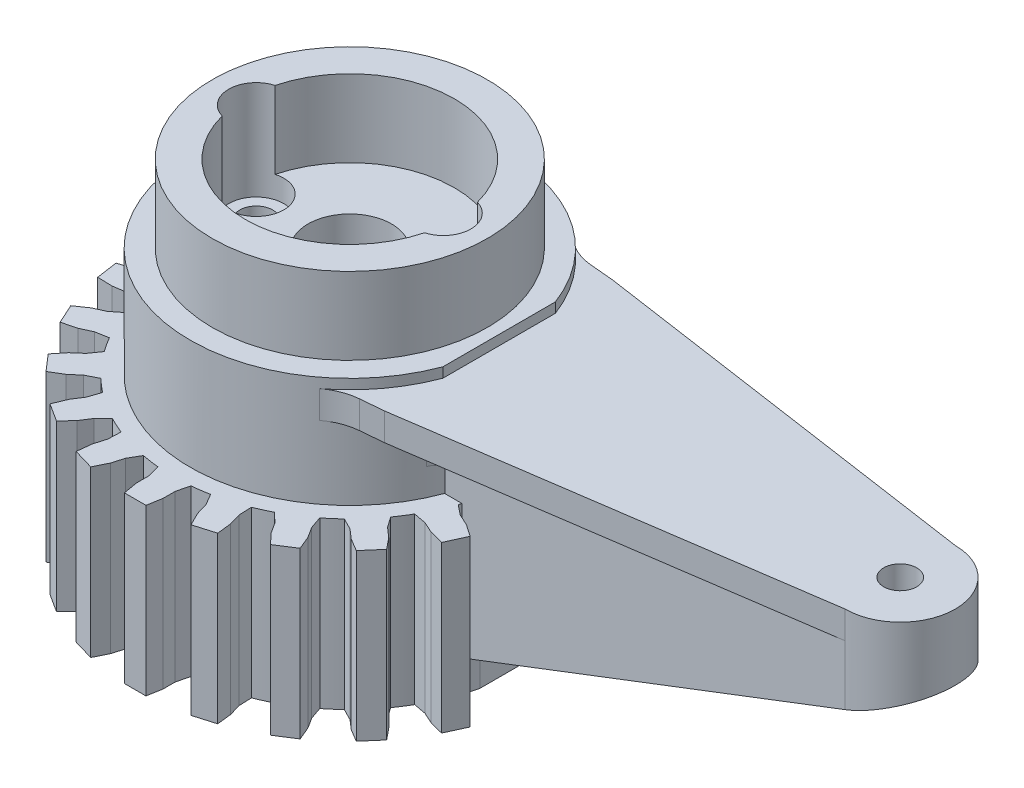
SolidWorks part; units mm, degrees
other "Markup1"
sketch "Sketch11" plane through (-17.3474, -40, -17.5082) normal (-0.1763, -0.9804, -0.0883) x (-0.1909, 0.1221, -0.974)
ref_plane "Front Plane" through (0, 0, 0) normal (0, 0, 1) x (1, 0, 0)
ref_plane "Top Plane" through (0, 0, 0) normal (0, 1, 0) x (1, 0, 0)
ref_plane "Right Plane" through (0, 0, 0) normal (1, 0, 0) x (0, 0, -1)
sketch "Sketch1" plane through (0, 0, 0) normal (0, 1, 0) x (1, 0, 0)
  circle A0 centre (0, 0) radius 14.5
extrude "Boss-Extrude1" add sketch "Sketch1" along normal blind 2 contours A0
sketch "Sketch2" plane through (0, 2, 0) normal (0, 1, 0) x (1, 0, 0)
  line L0 (0, 0) -> (-8.5, 0) construction
  line L1 (0, 0) -> (0, -2.0986) construction
  circle A0 centre (0, 0) radius 3.8
  circle A1 centre (-8.5, 0) radius 1.5
  circle A2 centre (8.5, 0) radius 1.5
  dimension "D1" = 8.5
extrude "Cut-Extrude1" cut sketch "Sketch2" against normal blind 2.5
sketch "Sketch3" plane through (0, 0, 0) normal (0, -1, 0) x (1, 0, 0)
  circle A0 centre (0, 0) radius 14.5
  circle A1 centre (0, 0) radius 12.5
  circle M3 centre (8.5, 0) radius 1.5
  circle M4 centre (-8.5, 0) radius 1.5
  circle M5 centre (0, 0) radius 3.8
  dimension "D1" = 2
extrude "Boss-Extrude2" add sketch "Sketch3" along normal blind 7 contours A1 M3 M5 M4 | A0 region at (-12.1464, 0, 0)
sketch "Sketch4" plane through (0, 2, 0) normal (0, 1, 0) x (1, 0, 0)
  circle A0 centre (0, 0) radius 3.8
  circle A1 centre (8.5, 0) radius 1.5
  circle A2 centre (-8.5, 0) radius 1.5
  circle A3 centre (0, 0) radius 14.5
extrude "Boss-Extrude3" add sketch "Sketch4" along normal blind 1 contours A3 | A2 | A1 | A0
sketch "Sketch5" plane through (0, 3, 0) normal (0, 1, 0) x (1, 0, 0)
  line L0 (0, 0) -> (0, 9.3425) construction
  circle A0 centre (8.5, 0) radius 2.6
  circle A1 centre (-8.5, 0) radius 2.5
extrude "Cut-Extrude2" cut sketch "Sketch5" against normal blind 2
sketch "Sketch6" plane through (0, 3, 0) normal (0, 1, 0) x (1, 0, 0)
  line L0 (0, 0) -> (30, 0) construction
  line L1 (30, 0) -> (45, 0) construction
  line L2 (45, 0) -> (60, 0) construction
  line L3 (60, 5) -> (13.6107, 5)
  line L4 (60, -5) -> (13.6107, -5)
  line L5 (60, 0) -> (73, 0) construction
  line L6 (60, 5) -> (70, 5)
  line L7 (60, -5) -> (70, -5)
  line L8 (70, 5) -> (73, 5)
  line L9 (70, -5) -> (73, -5)
  circle A4 centre (0, 0) radius 14.5 construction
  circle A6 centre (73, 0) radius 1.5
  arc A8 (73, -5) -> (73, 5) centre (73, 0) ccw
  circle M3 centre (0, 0) radius 14.5
  dimension "D1" = 15
  dimension "D2" = 15
  dimension "D3" = 30
  dimension "D4" = 13
extrude "Boss-Extrude4" add sketch "Sketch6" against normal blind 3.5 contours L4 L3 M3 region at (45.2639, 3, 0)
sketch "Sketch9" plane through (0, -7, 0) normal (0, -1, 0) x (-1, 0, 0)
  line L0 (0, 15.9926) -> (0, 19.4946) construction
  line L1 (0.9773, 19.4946) -> (-0.9773, 19.4946)
  line L2 (-0.9773, 19.4946) -> (-1.2082, 18.1848)
  line L45 (-0.9773, 19.4946) -> (-0.9773, 18.0837) construction
  line L46 (-1.2082, 18.1848) -> (-1.2082, 17.0658)
  line L47 (-1.2082, 17.0658) -> (-1.4932, 15.9228)
  line L48 (-1.2082, 17.0658) -> (-1.2082, 16.2048) construction
  line L49 (1.2082, 17.0658) -> (1.4932, 15.9228)
  line L50 (1.2082, 18.1848) -> (1.2082, 17.0658)
  line L51 (0.9773, 19.4946) -> (1.2082, 18.1848)
  line L52 (5.9673, 16.0341) -> (5.9187, 14.8571)
  line L53 (6.2825, 17.1078) -> (5.9673, 16.0341)
  line L54 (6.4299, 18.4296) -> (6.2825, 17.1078)
  line L55 (6.4299, 18.4296) -> (4.5546, 18.9802)
  line L56 (4.5546, 18.9802) -> (3.964, 17.7886)
  line L57 (3.964, 17.7886) -> (3.6487, 16.7149)
  line L58 (3.6487, 16.7149) -> (3.0533, 15.6985)
  line L59 (10.2429, 13.7034) -> (9.8646, 12.5878)
  line L60 (10.8478, 14.6448) -> (10.2429, 13.7034)
  line L61 (11.3617, 15.8715) -> (10.8478, 14.6448)
  line L62 (11.3617, 15.8715) -> (9.7174, 16.9282)
  line L63 (9.7174, 16.9282) -> (8.815, 15.9512)
  line L64 (8.815, 15.9512) -> (8.21, 15.0098)
  line L65 (8.21, 15.0098) -> (7.3523, 14.2024)
  line L66 (13.6887, 10.2626) -> (13.0115, 9.2987)
  line L67 (14.5343, 10.9954) -> (13.6887, 10.2626)
  line L68 (15.373, 12.0277) -> (14.5343, 10.9954)
  line L69 (15.373, 12.0277) -> (14.093, 13.5048)
  line L70 (14.093, 13.5048) -> (12.9519, 12.8216)
  line L71 (12.9519, 12.8216) -> (12.1062, 12.0888)
  line L72 (12.1062, 12.0888) -> (11.0558, 11.5557)
  line L73 (16.0255, 5.9904) -> (15.1042, 5.2563)
  line L74 (17.0434, 6.4552) -> (16.0255, 5.9904)
  line L75 (18.1389, 7.2094) -> (17.0434, 6.4552)
  line L76 (18.1389, 7.2094) -> (17.3269, 8.9873)
  line L77 (17.3269, 8.9873) -> (16.0395, 8.6533)
  line L78 (16.0395, 8.6533) -> (15.0217, 8.1884)
  line L79 (15.0217, 8.1884) -> (13.8636, 7.9728)
  line L80 (17.064, 1.2328) -> (15.9732, 0.7881)
  line L81 (18.1716, 1.3921) -> (17.064, 1.2328)
  line L82 (19.4352, 1.8071) -> (18.1716, 1.3921)
  line L83 (19.4352, 1.8071) -> (19.1571, 3.7417)
  line L84 (19.1571, 3.7417) -> (17.8277, 3.7839)
  line L85 (17.8277, 3.7839) -> (16.7201, 3.6246)
  line L86 (16.7201, 3.6246) -> (15.5482, 3.744)
  line L87 (16.7201, -3.6246) -> (15.5482, -3.744)
  line L88 (17.8277, -3.7839) -> (16.7201, -3.6246)
  line L89 (19.1571, -3.7417) -> (17.8277, -3.7839)
  line L90 (19.1571, -3.7417) -> (19.4352, -1.8071)
  line L91 (19.4352, -1.8071) -> (18.1716, -1.3921)
  line L92 (18.1716, -1.3921) -> (17.064, -1.2328)
  line L93 (17.064, -1.2328) -> (15.9732, -0.7881)
  line L94 (15.0217, -8.1884) -> (13.8636, -7.9728)
  line L95 (16.0395, -8.6533) -> (15.0217, -8.1884)
  line L96 (17.3269, -8.9873) -> (16.0395, -8.6533)
  line L97 (17.3269, -8.9873) -> (18.1389, -7.2094)
  line L98 (18.1389, -7.2094) -> (17.0434, -6.4552)
  line L99 (17.0434, -6.4552) -> (16.0255, -5.9904)
  line L100 (16.0255, -5.9904) -> (15.1042, -5.2563)
  line L101 (12.1062, -12.0888) -> (11.0558, -11.5557)
  line L102 (12.9519, -12.8216) -> (12.1062, -12.0888)
  line L103 (14.093, -13.5048) -> (12.9519, -12.8216)
  line L104 (14.093, -13.5048) -> (15.373, -12.0277)
  line L105 (15.373, -12.0277) -> (14.5343, -10.9954)
  line L106 (14.5343, -10.9954) -> (13.6887, -10.2626)
  line L107 (13.6887, -10.2626) -> (13.0115, -9.2987)
  line L108 (8.21, -15.0098) -> (7.3523, -14.2024)
  line L109 (8.815, -15.9512) -> (8.21, -15.0098)
  line L110 (9.7174, -16.9282) -> (8.815, -15.9512)
  line L111 (9.7174, -16.9282) -> (11.3617, -15.8715)
  line L112 (11.3617, -15.8715) -> (10.8478, -14.6448)
  line L113 (10.8478, -14.6448) -> (10.2429, -13.7034)
  line L114 (10.2429, -13.7034) -> (9.8646, -12.5878)
  line L115 (3.6487, -16.7149) -> (3.0533, -15.6985)
  line L116 (3.964, -17.7886) -> (3.6487, -16.7149)
  line L117 (4.5546, -18.9802) -> (3.964, -17.7886)
  line L118 (4.5546, -18.9802) -> (6.4299, -18.4296)
  line L119 (6.4299, -18.4296) -> (6.2825, -17.1078)
  line L120 (6.2825, -17.1078) -> (5.9673, -16.0341)
  line L121 (5.9673, -16.0341) -> (5.9187, -14.8571)
  line L122 (-1.2082, -17.0658) -> (-1.4932, -15.9228)
  line L123 (-1.2082, -18.1848) -> (-1.2082, -17.0658)
  line L124 (-0.9773, -19.4946) -> (-1.2082, -18.1848)
  line L125 (-0.9773, -19.4946) -> (0.9773, -19.4946)
  line L126 (0.9773, -19.4946) -> (1.2082, -18.1848)
  line L127 (1.2082, -18.1848) -> (1.2082, -17.0658)
  line L128 (1.2082, -17.0658) -> (1.4932, -15.9228)
  line L129 (-5.9673, -16.0341) -> (-5.9187, -14.8571)
  line L130 (-6.2825, -17.1078) -> (-5.9673, -16.0341)
  line L131 (-6.4299, -18.4296) -> (-6.2825, -17.1078)
  line L132 (-6.4299, -18.4296) -> (-4.5546, -18.9802)
  line L133 (-4.5546, -18.9802) -> (-3.964, -17.7886)
  line L134 (-3.964, -17.7886) -> (-3.6487, -16.7149)
  line L135 (-3.6487, -16.7149) -> (-3.0533, -15.6985)
  line L136 (-10.2429, -13.7034) -> (-9.8646, -12.5878)
  line L137 (-10.8478, -14.6448) -> (-10.2429, -13.7034)
  line L138 (-11.3617, -15.8715) -> (-10.8478, -14.6448)
  line L139 (-11.3617, -15.8715) -> (-9.7174, -16.9282)
  line L140 (-9.7174, -16.9282) -> (-8.815, -15.9512)
  line L141 (-8.815, -15.9512) -> (-8.21, -15.0098)
  line L142 (-8.21, -15.0098) -> (-7.3523, -14.2024)
  line L143 (-13.6887, -10.2626) -> (-13.0115, -9.2987)
  line L144 (-14.5343, -10.9954) -> (-13.6887, -10.2626)
  line L145 (-15.373, -12.0277) -> (-14.5343, -10.9954)
  line L146 (-15.373, -12.0277) -> (-14.093, -13.5048)
  line L147 (-14.093, -13.5048) -> (-12.9519, -12.8216)
  line L148 (-12.9519, -12.8216) -> (-12.1062, -12.0888)
  line L149 (-12.1062, -12.0888) -> (-11.0558, -11.5557)
  line L150 (-16.0255, -5.9904) -> (-15.1042, -5.2563)
  line L151 (-17.0434, -6.4552) -> (-16.0255, -5.9904)
  line L152 (-18.1389, -7.2094) -> (-17.0434, -6.4552)
  line L153 (-18.1389, -7.2094) -> (-17.3269, -8.9873)
  line L154 (-17.3269, -8.9873) -> (-16.0395, -8.6533)
  line L155 (-16.0395, -8.6533) -> (-15.0217, -8.1884)
  line L156 (-15.0217, -8.1884) -> (-13.8636, -7.9728)
  line L157 (-17.064, -1.2328) -> (-15.9732, -0.7881)
  line L158 (-18.1716, -1.3921) -> (-17.064, -1.2328)
  line L159 (-19.4352, -1.8071) -> (-18.1716, -1.3921)
  line L160 (-19.4352, -1.8071) -> (-19.1571, -3.7417)
  line L161 (-19.1571, -3.7417) -> (-17.8277, -3.7839)
  line L162 (-17.8277, -3.7839) -> (-16.7201, -3.6246)
  line L163 (-16.7201, -3.6246) -> (-15.5482, -3.744)
  line L164 (-16.7201, 3.6246) -> (-15.5482, 3.744)
  line L165 (-17.8277, 3.7839) -> (-16.7201, 3.6246)
  line L166 (-19.1571, 3.7417) -> (-17.8277, 3.7839)
  line L167 (-19.1571, 3.7417) -> (-19.4352, 1.8071)
  line L168 (-19.4352, 1.8071) -> (-18.1716, 1.3921)
  line L169 (-18.1716, 1.3921) -> (-17.064, 1.2328)
  line L170 (-17.064, 1.2328) -> (-15.9732, 0.7881)
  line L171 (-15.0217, 8.1884) -> (-13.8636, 7.9728)
  line L172 (-16.0395, 8.6533) -> (-15.0217, 8.1884)
  line L173 (-17.3269, 8.9873) -> (-16.0395, 8.6533)
  line L174 (-17.3269, 8.9873) -> (-18.1389, 7.2094)
  line L175 (-18.1389, 7.2094) -> (-17.0434, 6.4552)
  line L176 (-17.0434, 6.4552) -> (-16.0255, 5.9904)
  line L177 (-16.0255, 5.9904) -> (-15.1042, 5.2563)
  line L178 (-12.1062, 12.0888) -> (-11.0558, 11.5557)
  line L179 (-12.9519, 12.8216) -> (-12.1062, 12.0888)
  line L180 (-14.093, 13.5048) -> (-12.9519, 12.8216)
  line L181 (-14.093, 13.5048) -> (-15.373, 12.0277)
  line L182 (-15.373, 12.0277) -> (-14.5343, 10.9954)
  line L183 (-14.5343, 10.9954) -> (-13.6887, 10.2626)
  line L184 (-13.6887, 10.2626) -> (-13.0115, 9.2987)
  line L185 (-8.21, 15.0098) -> (-7.3523, 14.2024)
  line L186 (-8.815, 15.9512) -> (-8.21, 15.0098)
  line L187 (-9.7174, 16.9282) -> (-8.815, 15.9512)
  line L188 (-9.7174, 16.9282) -> (-11.3617, 15.8715)
  line L189 (-11.3617, 15.8715) -> (-10.8478, 14.6448)
  line L190 (-10.8478, 14.6448) -> (-10.2429, 13.7034)
  line L191 (-10.2429, 13.7034) -> (-9.8646, 12.5878)
  line L192 (-3.6487, 16.7149) -> (-3.0533, 15.6985)
  line L193 (-3.964, 17.7886) -> (-3.6487, 16.7149)
  line L194 (-4.5546, 18.9802) -> (-3.964, 17.7886)
  line L195 (-4.5546, 18.9802) -> (-6.4299, 18.4296)
  line L196 (-6.4299, 18.4296) -> (-6.2825, 17.1078)
  line L197 (-6.2825, 17.1078) -> (-5.9673, 16.0341)
  line L198 (-5.9673, 16.0341) -> (-5.9187, 14.8571)
  arc A2 (-9.8646, 12.5878) -> (-11.0558, 11.5557) centre (0, 0) ccw
  arc A17 (-13.0115, 9.2987) -> (-13.8636, 7.9728) centre (0, 0) ccw
  circle A18 centre (0, 0) radius 20
  arc A19 (-5.9187, 14.8571) -> (-7.3523, 14.2024) centre (0, 0) ccw
  arc A20 (-1.4932, 15.9228) -> (-3.0533, 15.6985) centre (0, 0) ccw
  arc A21 (3.0533, 15.6985) -> (1.4932, 15.9228) centre (0, 0) ccw
  arc A22 (7.3523, 14.2024) -> (5.9187, 14.8571) centre (0, 0) ccw
  arc A23 (11.0558, 11.5557) -> (9.8646, 12.5878) centre (0, 0) ccw
  arc A24 (13.8636, 7.9728) -> (13.0115, 9.2987) centre (0, 0) ccw
  arc A25 (15.5482, 3.744) -> (15.1042, 5.2563) centre (0, 0) ccw
  arc A26 (15.9732, -0.7881) -> (15.9732, 0.7881) centre (0, 0) ccw
  arc A27 (15.1042, -5.2563) -> (15.5482, -3.744) centre (0, 0) ccw
  arc A28 (13.0115, -9.2987) -> (13.8636, -7.9728) centre (0, 0) ccw
  arc A29 (9.8646, -12.5878) -> (11.0558, -11.5557) centre (0, 0) ccw
  arc A30 (5.9187, -14.8571) -> (7.3523, -14.2024) centre (0, 0) ccw
  arc A31 (1.4932, -15.9228) -> (3.0533, -15.6985) centre (0, 0) ccw
  arc A32 (-3.0533, -15.6985) -> (-1.4932, -15.9228) centre (0, 0) ccw
  arc A33 (-7.3523, -14.2024) -> (-5.9187, -14.8571) centre (0, 0) ccw
  arc A34 (-11.0558, -11.5557) -> (-9.8646, -12.5878) centre (0, 0) ccw
  arc A35 (-13.8636, -7.9728) -> (-13.0115, -9.2987) centre (0, 0) ccw
  arc A36 (-15.5482, -3.744) -> (-15.1042, -5.2563) centre (0, 0) ccw
  arc A37 (-15.9732, 0.7881) -> (-15.9732, -0.7881) centre (0, 0) ccw
  arc A38 (-15.1042, 5.2563) -> (-15.5482, 3.744) centre (0, 0) ccw
  circle A39 centre (0, 0) radius 12.5
  point P188 (0, 0)
  dimension "D2" = 1.33
  dimension "D1" = 10
  dimension "D3" = 1.119
  dimension "D5" = 1.178
  dimension "D4" = 14
  dimension "D6" = 22
extrude "Boss-Extrude5" add sketch "Sketch9" along normal blind 30 contours L184 A17 L171 L172 L173 L174 L175 L176 L177 A38 L164 L165 L166 L167 L168 L169 L170 A37 L157 L158 L159 L160 L161 L162 L163 A36 L150 L151 L152 L153 L154 L155 L156 A35 L143 L144 L145 L146 L147 L148 L149 A34 L136 L137 L138 L139 L140 L141 L142 A33 L129 L130 L131 L132 L133 L134 L135 A32 L122 L123 L124 L125 L126 L127 L128 A31 L115 L116 L117 L118 L119 L120 L121 A30 L108 L109 L110 L111 L112 L113 L114 A29 L101 L102 L103 L104 L105 L106 L107 A28 L94 L95 L96 L97 L98 L99 L100 A27 L87 L88 L89 L90 L91 L92 L93 A26 L80 L81 L82 L83 L84 L85 L86 A25 L73 L74 L75 L76 L77 L78 L79 A24 L66 L67 L68 L69 L70 L71 L72 A23 L59 L60 L61 L62 L63 L64 L65 A22 L52 L53 L54 L55 L56 L57 L58 A21 L49 L50 L51 L1 L2 L46 L47 A20 L192 L193 L194 L195 L196 L197 L198 A19 L185 L186 L187 L188 L189 L190 L191 A2 L178 L179 L180 L181 L182 L183 | A39
sketch "Sketch15" plane through (0, 3, 0) normal (0, 1, 0) x (1, 0, 0)
  circle A0 centre (0, 0) radius 12.5
  circle A2 centre (0, 0) radius 9.5
  dimension "D1" = 3
extrude "Boss-Extrude9" add sketch "Sketch15" along normal blind 7 contours A0 | A2
sketch "Sketch17" plane through (0, 10, 0) normal (0, 1, 0) x (1, 0, 0)
  line L0 (0, 0) -> (-8.5, 0) construction
  line L1 (0, 0) -> (0, -2.0291) construction
  circle A0 centre (-8.5, 0) radius 2.5
  circle A1 centre (8.5, 0) radius 2.5
  dimension "D1" = 8.5
extrude "Cut-Extrude5" cut sketch "Sketch17" against normal blind 7
sketch "Sketch18" plane through (0, 3, 0) normal (0, 1, 0) x (1, 0, 0)
  line L1 (13.5686, 6.8144) -> (85.2134, 6.8144)
  line L2 (13.5686, 6.8144) -> (13.5686, -6.7184)
  line L3 (13.5686, -6.7184) -> (85.2134, -6.7184)
  line L4 (85.2134, 6.8144) -> (85.2134, -6.7184)
extrude "Cut-Extrude6" cut sketch "Sketch18" against normal blind 0.9
sketch "Sketch19" plane through (0, -37, 0) normal (0, -1, 0) x (1, 0, 0)
  line L1 (-30.1927, 29.9961) -> (31.3867, 29.9961)
  line L2 (-30.1927, 29.9961) -> (-30.1927, -24.9381)
  line L3 (-30.1927, -24.9381) -> (31.3867, -24.9381)
  line L4 (31.3867, 29.9961) -> (31.3867, -24.9381)
extrude "Cut-Extrude7" cut sketch "Sketch19" against normal blind 15
sketch "Sketch20" plane through (0, 2.1, 0) normal (0, 1, 0) x (1, 0, 0)
  line L0 (13.5686, 0) -> (46.2278, 0) construction
  line L1 (13.5686, 5.1131) -> (13.5686, -5.1131) construction
  line L3 (73, 5) -> (9.8263, 10.6628)
  line L4 (73, 5) -> (13.5686, 4.68)
  line L5 (13.5686, 4.68) -> (13.5686, 5.1131)
  line L6 (73, -5) -> (13.5686, -4.68)
  line L7 (73, -5) -> (9.8263, -10.6628)
  line L8 (13.5686, -4.68) -> (13.5686, -5.1131)
  circle A0 centre (0, 0) radius 14.5 construction
  arc A1 (13.5686, 5.1131) -> (9.8263, 10.6628) centre (0, 0) ccw
  arc A2 (13.5686, -5.1131) -> (9.8263, -10.6628) centre (0, 0) cw
extrude "Boss-Extrude14" add sketch "Sketch20" against normal blind 2.5 contours L5 A1 L3 L4 | L6 L8 A2 L7
fillet "Fillet2" radius 5 2 edges at (9.8263, 0.85, -10.6628) (9.8263, 0.85, 10.6628)
sketch "Sketch21" plane through (0, -0.5, 0) normal (0, -1, 0) x (1, 0, 0)
  line L0 (13.6107, 5) -> (73, 5) construction
  line L1 (13.6107, 5) -> (54.7559, 5)
  line L2 (13.6107, 5) -> (13.6107, -5)
  line L3 (13.6107, -5) -> (54.7559, -5)
  line L4 (54.7559, 5) -> (54.7559, -5)
  line L5 (73, -5) -> (13.6107, -5) construction
extrude "Boss-Extrude15" add sketch "Sketch21" along normal blind 4
sketch "Sketch22" plane through (0, 0, 5) normal (0, 0, 1) x (1, 0, 0)
  line L0 (13.6107, -4.5) -> (54.7559, -0.5)
  line L1 (54.7559, -0.5) -> (54.7559, -4.5)
  line L2 (54.7559, -4.5) -> (13.6107, -4.5)
extrude "Cut-Extrude8" cut sketch "Sketch22" against normal blind 17
fillet "Fillet5" radius 2 2 edges at (13.6107, -2.45, 5) (13.6107, -2.45, -5)
sketch "Sketch23" plane through (0, 2.1, 0) normal (0, 1, 0) x (1, 0, 0)
  line L0 (0, 0) -> (50, 0) construction
  line L1 (10.017, 10.8428) -> (50, 5)
  line L2 (10.017, -10.8428) -> (50, -5)
  line L3 (10.017, 10.8428) -> (87.3152, 10.8428)
  line L4 (87.3152, 10.8428) -> (87.3152, -12.7535)
  line L5 (87.3152, -12.7535) -> (10.017, -10.8428)
  circle A0 centre (50, 0) radius 1.5
  circle A1 centre (50, 0) radius 5
  arc A2 (8.795, 11.5282) -> (11.3813, 10.5234) centre (11.8277, 15.5034) ccw construction
  arc A3 (11.3813, -10.5234) -> (8.795, -11.5282) centre (11.8277, -15.5034) ccw construction
  line M5 (11.3813, -10.5234) -> (73, -5)
  arc M6 (73, -5) -> (73, 5) centre (73, 0) ccw
  line M7 (73, 5) -> (11.3813, 10.5234)
  circle M10 centre (73, 0) radius 1.5
  dimension "D1" = 50
extrude "Cut-Extrude9" cut sketch "Sketch23" against normal blind 8 contours L5 L4 L3 L1 L2 M7 M6 M5 | A1 L2 L1 M5 M6 M7 M10 region at (48.6661, 2.1, -10.0346) region at (58.2003, 2.1, 0)
sketch "Sketch24" plane through (0, 2.1, 0) normal (0, 1, 0) x (1, 0, 0)
  line L0 (0, 0) -> (50, 0) construction
  circle A0 centre (50, 0) radius 1.5
  dimension "D1" = 50
extrude "Cut-Extrude10" cut sketch "Sketch24" against normal blind 8 contours A0
sketch "Sketch27" plane through (0, -0.4, 0) normal (0, -1, 0) x (1, 0, 0)
  line L0 (50, -5) -> (14.9416, -5) construction
  line L1 (44.8577, -5) -> (13.6365, -5)
  line L2 (44.8577, -5) -> (44.8577, 5)
  line L3 (44.8577, 5) -> (13.6365, 5)
  line L4 (13.6365, -5) -> (13.6365, 5)
extrude "Boss-Extrude16" add sketch "Sketch27" along normal blind 19
sketch "Sketch28" plane through (0, 0, -5) normal (0, 0, -1) x (-1, 0, 0)
  line L0 (-44.8577, -1.4623) -> (-14.093, -19.8022)
  line L1 (-14.093, -22) -> (-14.093, -7) construction
  line L2 (-44.8577, -1.4623) -> (-14.093, -1.4623)
  line L3 (-14.093, -1.4623) -> (-14.093, -19.8022)
  line L4 (-44.8577, -1.4623) -> (-44.8577, -19.4)
  line L5 (-44.8577, -19.4) -> (-14.093, -19.8022)
  line M8 (-44.8577, -1.4623) -> (-44.8577, -19.4)
  line M9 (-44.8577, -19.4) -> (-15.1909, -19.4)
  line M10 (-15.1909, -19.4) -> (-15.1909, -7)
extrude "Cut-Extrude11" cut sketch "Sketch28" against normal blind 10 contours L0 M8 M9 M10 region at (34.8316, -13.4196, -5)
sketch "Sketch29" plane through (0, -22, 0) normal (0, -1, 0) x (1, 0, 0)
  line L0 (15.5482, 3.744) -> (15.5482, -3.744)
  line L1 (15.5482, -3.744) -> (22.3513, -4.3151)
  line L2 (22.3513, -4.3151) -> (21.8437, 6.0073)
  line L3 (21.8437, 6.0073) -> (15.5482, 3.744)
extrude "Cut-Extrude12" cut sketch "Sketch29" against normal blind 3
sketch "Sketch33" plane through (0, 2.1, 0) normal (0, 1, 0) x (1, 0, 0)
  circle A0 centre (50, 0) radius 1.5
  circle A1 centre (50, 0) radius 5
  circle M2 centre (50, 0) radius 1.5
extrude "Boss-Extrude19" add sketch "Sketch33" against normal blind 6 contours M2 | A1 region at (50, 2.1, 0)
sketch "Sketch34" plane through (0, -3.9, 0) normal (0, -1, 0) x (1, 0, 0)
  line L0 (50, 5) -> (36.3441, 5)
  line L1 (14.9416, 5) -> (50, 5) construction
  line L2 (50, -5) -> (36.3441, -5)
  line L4 (50, -5) -> (14.9416, -5) construction
  line L5 (36.3441, -5) -> (36.3441, 5)
  circle A0 centre (50, 0) radius 5 construction
  arc A1 (50, 5) -> (50, -5) centre (50, 0) ccw construction
  circle A2 centre (50, 0) radius 5
  circle M2 centre (50, 0) radius 5
extrude "Boss-Extrude20" add sketch "Sketch34" against normal blind 5 contours L5 L2 L0 M2 region at (41.2726, -3.9, 0)
sketch "Sketch35" plane through (0, 0, -5) normal (0, 0, -1) x (-1, 0, 0)
  line L0 (-15.1909, -19.1477) -> (-14.9881, -3.9)
  line L5 (-55, -3.9) -> (-15.1909, -19.1477)
  line L6 (-55, -3.9) -> (-14.9881, -3.9)
extrude "Boss-Extrude21" add sketch "Sketch35" against normal blind 10
sketch "Sketch36" plane through (0, 2.1, 0) normal (0, 1, 0) x (1, 0, 0)
  line L0 (50, 5) -> (55, 5)
  line L1 (55, 5) -> (55, -5)
  line L2 (55, -5) -> (50, -5)
  circle A0 centre (50, 0) radius 1.5
  arc A1 (50, -5) -> (50, 5) centre (50, 0) ccw
  arc M4 (50, -5) -> (50, 5) centre (50, 0) ccw
  circle M13 centre (50, 0) radius 1.5
extrude "Cut-Extrude13" cut sketch "Sketch36" against normal blind 10 contours L1 L0 M4 | M13 | L2 L1 M4 | L2 A1 L0 L1 region at (53.8832, 2.1, 3.8832) region at (53.8832, 2.1, -3.8832) region at (50, 2.1, 0)
